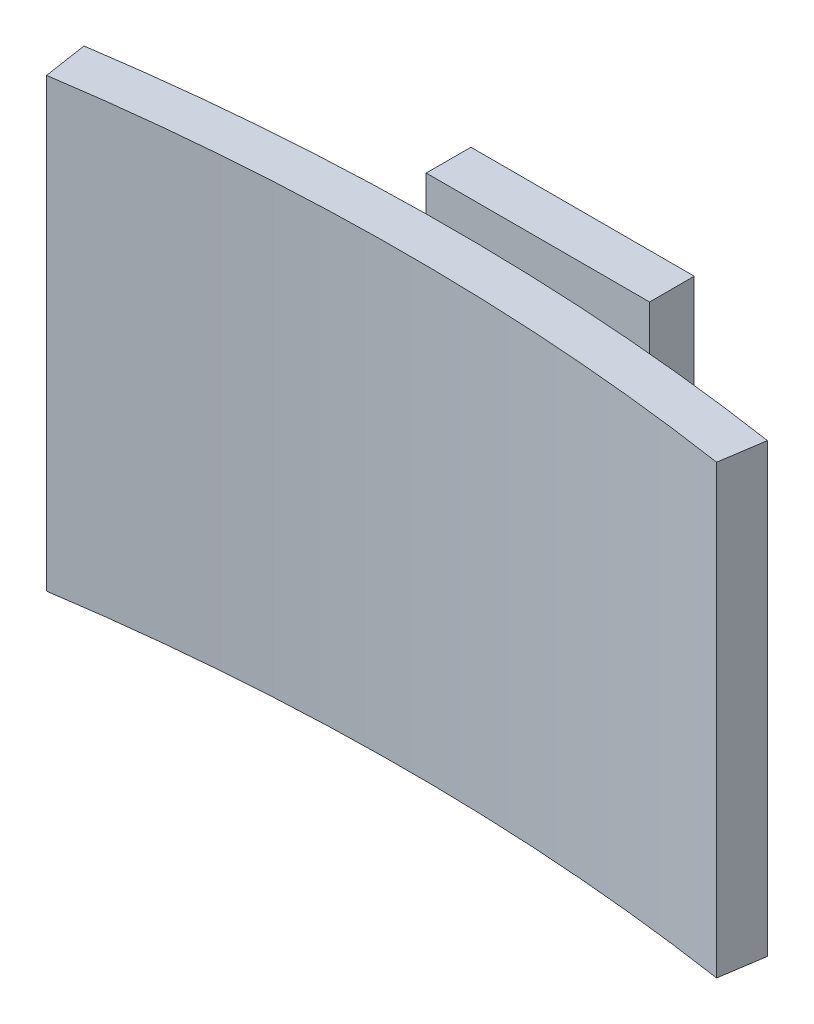
SolidWorks part; units mm, degrees
ref_plane "Front Plane" through (0, 0, 0) normal (0, 0, 1) x (1, 0, 0)
ref_plane "Top Plane" through (0, 0, 0) normal (0, 1, 0) x (1, 0, 0)
ref_plane "Right Plane" through (0, 0, 0) normal (1, 0, 0) x (0, 0, -1)
sketch "Sketch2" plane through (0, 0, 0) normal (0, 1, 0) x (1, 0, 0)
  line L0 (0, 0) -> (0, -98.8686) construction
  line L1 (-15, 0) -> (15, 0) construction
  line L2 (-15.3, 1.9774) -> (-15, 0)
  line L3 (15, 0) -> (15.3, 1.9774)
  arc A0 (-15, 0) -> (15, 0) centre (0, -98.8686) cw
  arc A1 (-15.3, 1.9774) -> (15.3, 1.9774) centre (0, -98.8686) cw
  point P5 (0, 0)
  dimension "D1" = 100
  dimension "D2" = 30
  dimension "D3" = 2
extrude "Boss-Extrude1" add sketch "Sketch2" along normal blind 20
sketch "Sketch3" plane through (0, 0, 0) normal (0, 0, 1) x (1, 0, 0)
  line L0 (0, 20) -> (0, 0) construction
  line L1 (15, 20) -> (-15, 20) construction
  line L3 (-5, 5.2131) -> (5, 5.2131)
  line L4 (-5, 5.2131) -> (-5, 7.7131)
  line L5 (-5, 7.7131) -> (5, 7.7131)
  line L6 (5, 5.2131) -> (5, 7.7131)
  line L7 (-5, 5.2131) -> (5, 7.7131) construction
  line L8 (-5, 7.7131) -> (5, 5.2131) construction
  point P5 (0, 6.4631)
  dimension "D1" = 2.5
  dimension "D2" = 10
extrude "Boss-Extrude2" add sketch "Sketch3" along normal up to surface (5.9912 mm away) from offset 9 up to face at (0, 10, -2.5544) offset against normal yes
sketch "Sketch4" plane through (0, 7.7131, 0) normal (0, 1, 0) x (1, 0, 0)
  line L0 (5, 3.0088) -> (5, 9) construction
  line L1 (-5, 9) -> (5, 9)
  line L2 (-5, 9) -> (-5, 7)
  line L3 (-5, 7) -> (5, 7)
  line L4 (5, 9) -> (5, 7)
  dimension "D1" = 2
extrude "Boss-Extrude3" add sketch "Sketch4" along normal blind 10
chamfer "Chamfer2" distance 3 angle 30 1 edges at (0, 7.7131, -7) first distance on face at (0, 12.7131, -7)
chamfer "Chamfer1" distance 4 angle 30 1 edges at (0, 5.2131, -9) first distance on face at (0, 11.4631, -9)
sketch "Sketch6" plane through (0, 0, -7) normal (0, 0, 1) x (1, 0, 0)
  line L0 (5, 17.7131) -> (5, 10.7131) construction
  line L1 (5, 12.7131) -> (-5, 12.7131)
  line L2 (5, 12.7131) -> (5, 13.7131)
  line L3 (5, 13.7131) -> (-5, 13.7131)
  line L4 (-5, 12.7131) -> (-5, 13.7131)
  line L5 (-5, 17.7131) -> (-5, 10.7131) construction
  line L6 (-5, 17.7131) -> (5, 17.7131) construction
  dimension "D1" = 5
  dimension "D2" = 1
extrude "Boss-Extrude4" add sketch "Sketch6" along normal blind 0.2
chamfer "Chamfer3" distance 0.5 angle 45 1 edges at (0, 13.7131, -6.8)
